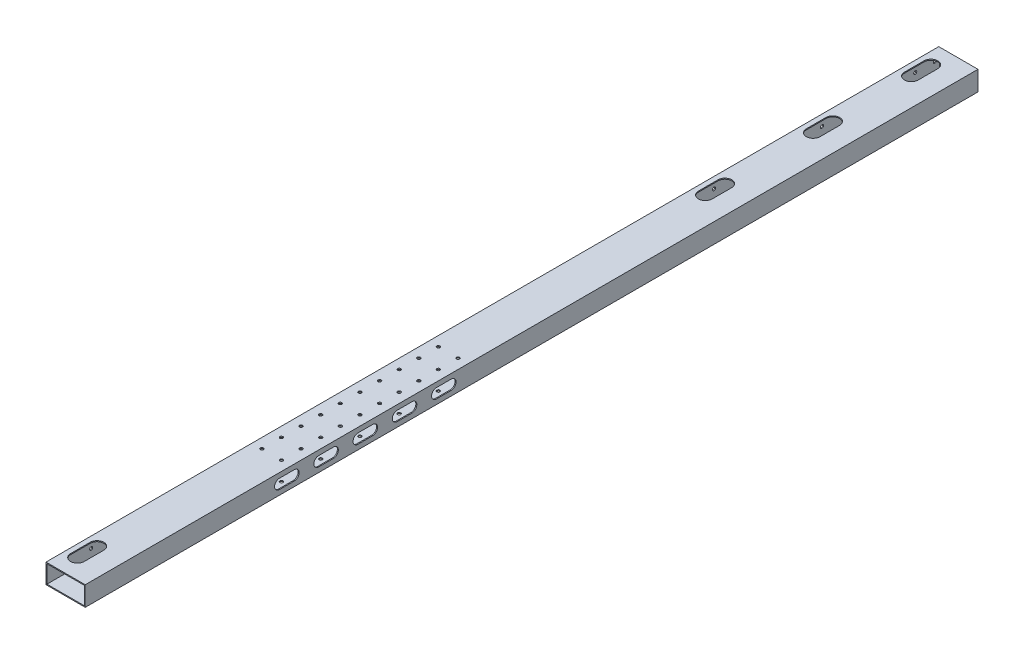
SolidWorks part; units mm, degrees
material "1060 合金"
ref_plane "前视基准面" through (0, 0, 0) normal (0, 0, 1) x (1, 0, 0)
ref_plane "上视基准面" through (0, 0, 0) normal (0, 1, 0) x (1, 0, 0)
ref_plane "右视基准面" through (0, 0, 0) normal (1, 0, 0) x (0, 0, -1)
other "Configuration Table"
sketch "草图1" plane through (0, 0, 0) normal (0, 0, 1) x (1, 0, 0)
  line L1 (-40, 20) -> (0, 20)
  line L2 (-40, 20) -> (-40, 0)
  line L3 (-40, 0) -> (0, 0)
  line L4 (0, 20) -> (0, 0)
  dimension "D1" = 20
  dimension "D2" = 40
extrude "拉伸-薄壁1" add sketch "草图1" along normal blind 910 thin thin type one direction reverse wall 1
sketch "草图2" plane through (-40, 0, 0) normal (-1, 0, 0) x (0, 0, 1)
  circle A0 centre (865, 10) radius 1.6 construction
  circle A1 centre (845, 10) radius 1.6 construction
  circle A2 centre (825, 10) radius 1.6 construction
  circle A3 centre (45, 10) radius 1.6 construction
  circle A4 centre (25, 10) radius 1.6 construction
  circle A5 centre (5, 10) radius 1.6 construction
  circle A6 centre (865, 10) radius 1.6
  circle A7 centre (845, 10) radius 1.6
  circle A8 centre (825, 10) radius 1.6
  circle A9 centre (45, 10) radius 1.6
  circle A10 centre (25, 10) radius 1.6
  circle A11 centre (5, 10) radius 1.6
extrude "切除-拉伸1" cut sketch "草图2" against normal up to next
sketch "草图3" plane through (-40, 0, 0) normal (-1, 0, 0) x (0, 0, 1)
  line L0 (0, 20) -> (0, 0) construction
  line L1 (910, 0) -> (0, 0) construction
  circle A0 centre (120, 10) radius 1.6
  circle A1 centre (140, 10) radius 1.6
  circle A2 centre (230, 10) radius 1.6
  circle A3 centre (250, 10) radius 1.6
  dimension "D3" = 3.2
  dimension "D4" = 3.2
  dimension "D1" = 120
  dimension "D2" = 20
  dimension "D5" = 10
  dimension "D6" = 10
  dimension "D7" = 2
extrude "切除-拉伸2" cut sketch "草图3" against normal blind 10
sketch "草图4" plane through (0, 0, 0) normal (0, -1, 0) x (1, 0, 0)
  line L0 (-28, 140) -> (-28, 120) construction
  line L1 (-22, 140) -> (-22, 120)
  line L2 (-34, 140) -> (-34, 120)
  line L3 (-40, 0) -> (0, 0) construction
  line L4 (-40, 910) -> (-40, 0) construction
  line L5 (-28, 250) -> (-28, 230) construction
  line L6 (-22, 250) -> (-22, 230)
  line L7 (-34, 250) -> (-34, 230)
  arc A0 (-22, 140) -> (-34, 140) centre (-28, 140) ccw
  arc A1 (-34, 120) -> (-22, 120) centre (-28, 120) ccw
  arc A2 (-22, 250) -> (-34, 250) centre (-28, 250) ccw
  arc A3 (-34, 230) -> (-22, 230) centre (-28, 230) ccw
  point P2 (-28, 130)
  point P15 (-28, 240)
  dimension "D2" = 6
  dimension "D1" = 20
  dimension "D3" = 120
  dimension "D4" = 12
  dimension "D5" = 2
extrude "切除-拉伸3" [suppressed] cut sketch "草图4" against normal up to next
sketch "草图5" plane through (0, 20, 0) normal (0, 1, 0) x (1, 0, 0)
  line L0 (-28, -120) -> (-28, -140) construction
  line L1 (-21, -120) -> (-21, -140)
  line L2 (-35, -120) -> (-35, -140)
  line L3 (-40, -910) -> (-40, 0) construction
  line L4 (0, 0) -> (-40, 0) construction
  line L5 (-28, -230) -> (-28, -250) construction
  line L6 (-21, -230) -> (-21, -250)
  line L7 (-35, -230) -> (-35, -250)
  line L8 (-28, -20) -> (-28, -40) construction
  line L9 (-21, -20) -> (-21, -40)
  line L10 (-35, -20) -> (-35, -40)
  line L11 (-28, -870) -> (-28, -890) construction
  line L12 (-21, -870) -> (-21, -890)
  line L13 (-35, -870) -> (-35, -890)
  arc A0 (-21, -120) -> (-35, -120) centre (-28, -120) ccw
  arc A1 (-35, -140) -> (-21, -140) centre (-28, -140) ccw
  arc A2 (-21, -230) -> (-35, -230) centre (-28, -230) ccw
  arc A3 (-35, -250) -> (-21, -250) centre (-28, -250) ccw
  arc A4 (-21, -20) -> (-35, -20) centre (-28, -20) ccw
  arc A5 (-35, -40) -> (-21, -40) centre (-28, -40) ccw
  arc A6 (-21, -870) -> (-35, -870) centre (-28, -870) ccw
  arc A7 (-35, -890) -> (-21, -890) centre (-28, -890) ccw
  point P2 (-28, -130)
  point P14 (-28, -240)
  point P21 (-28, -30)
  point P29 (-28, -880)
  dimension "D2" = 7
  dimension "D1" = 12
  dimension "D3" = 120
  dimension "D4" = 20
  dimension "D5" = 2
  dimension "D6" = 2
  dimension "D7" = 2
extrude "切除-拉伸4" cut sketch "草图5" against normal blind 10
sketch "草图6" plane through (0, 20, 0) normal (0, 1, 0) x (1, 0, 0)
  line L0 (-40, -910) -> (-40, 0) construction
  line L1 (0, -910) -> (-40, -910) construction
  circle A0 centre (-30, -700) radius 1.6
  circle A1 centre (-10, -700) radius 1.6
  circle A2 centre (-10, -680) radius 1.6
  circle A3 centre (-10, -660) radius 1.6
  circle A4 centre (-10, -640) radius 1.6
  circle A5 centre (-10, -620) radius 1.6
  circle A6 centre (-10, -600) radius 1.6
  circle A7 centre (-10, -580) radius 1.6
  circle A8 centre (-10, -560) radius 1.6
  circle A9 centre (-10, -540) radius 1.6
  circle A10 centre (-10, -520) radius 1.6
  circle A11 centre (-30, -680) radius 1.6
  circle A12 centre (-30, -660) radius 1.6
  circle A13 centre (-30, -640) radius 1.6
  circle A14 centre (-30, -620) radius 1.6
  circle A15 centre (-30, -600) radius 1.6
  circle A16 centre (-30, -580) radius 1.6
  circle A17 centre (-30, -560) radius 1.6
  circle A18 centre (-30, -540) radius 1.6
  circle A19 centre (-30, -520) radius 1.6
  dimension "D1" = 3.2
  dimension "D2" = 10
  dimension "D3" = 210
  dimension "D4" = 2
  dimension "D5" = 10
extrude "切除-拉伸5" cut sketch "草图6" against normal through all
sketch "草图7" plane through (0, 0, 0) normal (1, 0, 0) x (0, 0, -1)
  line L0 (-712, 10) -> (-697, 10) construction
  line L1 (-712, 15) -> (-697, 15)
  line L2 (-712, 5) -> (-697, 5)
  line L3 (-910, 0) -> (0, 0) construction
  line L4 (-910, 0) -> (-910, 20) construction
  line L5 (-672, 10) -> (-657, 10) construction
  line L6 (-672, 15) -> (-657, 15)
  line L7 (-672, 5) -> (-657, 5)
  line L8 (-632, 10) -> (-617, 10) construction
  line L9 (-632, 15) -> (-617, 15)
  line L10 (-632, 5) -> (-617, 5)
  line L11 (-592, 10) -> (-577, 10) construction
  line L12 (-592, 15) -> (-577, 15)
  line L13 (-592, 5) -> (-577, 5)
  line L14 (-552, 10) -> (-537, 10) construction
  line L15 (-552, 15) -> (-537, 15)
  line L16 (-552, 5) -> (-537, 5)
  arc A0 (-712, 15) -> (-712, 5) centre (-712, 10) ccw
  arc A1 (-697, 5) -> (-697, 15) centre (-697, 10) ccw
  arc A2 (-672, 15) -> (-672, 5) centre (-672, 10) ccw
  arc A3 (-657, 5) -> (-657, 15) centre (-657, 10) ccw
  arc A4 (-632, 15) -> (-632, 5) centre (-632, 10) ccw
  arc A5 (-617, 5) -> (-617, 15) centre (-617, 10) ccw
  arc A6 (-592, 15) -> (-592, 5) centre (-592, 10) ccw
  arc A7 (-577, 5) -> (-577, 15) centre (-577, 10) ccw
  arc A8 (-552, 15) -> (-552, 5) centre (-552, 10) ccw
  arc A9 (-537, 5) -> (-537, 15) centre (-537, 10) ccw
  point P2 (-704.5, 10)
  point P14 (-664.5, 10)
  point P21 (-624.5, 10)
  point P28 (-584.5, 10)
  point P35 (-544.5, 10)
  dimension "D2" = 5
  dimension "D1" = 10
  dimension "D3" = 198
  dimension "D4" = 15
  dimension "D5" = 5
extrude "切除-拉伸6" cut sketch "草图7" against normal up to next
